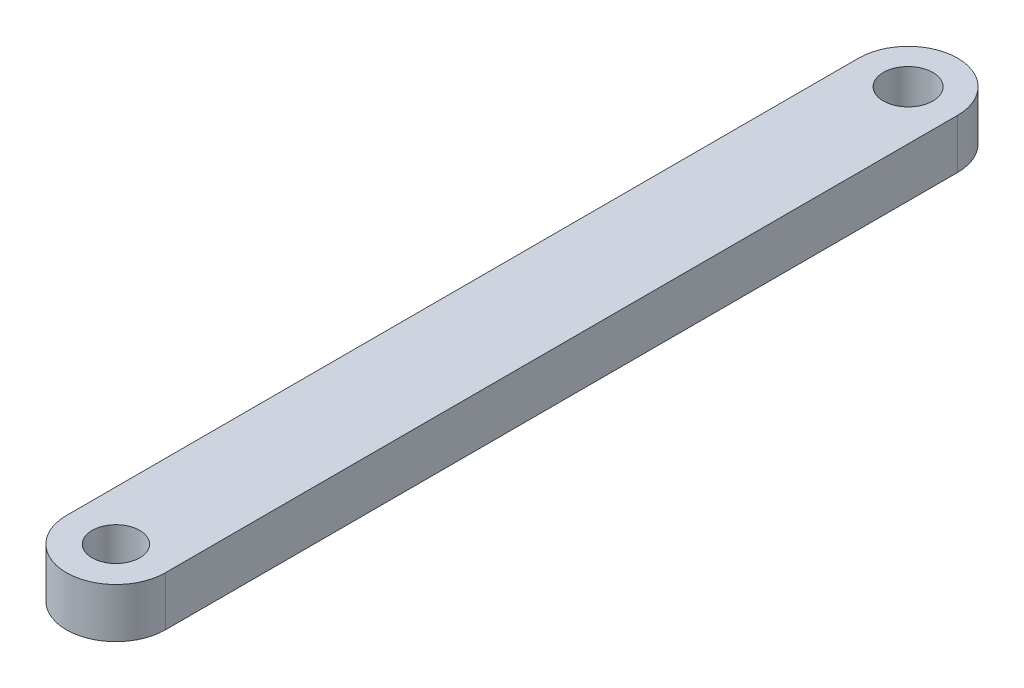
SolidWorks part; units mm, degrees
ref_plane "Front Plane" through (0, 0, 0) normal (0, 0, 1) x (1, 0, 0)
ref_plane "Top Plane" through (0, 0, 0) normal (0, 1, 0) x (1, 0, 0)
ref_plane "Right Plane" through (0, 0, 0) normal (1, 0, 0) x (0, 0, -1)
sketch "Sketch1" plane through (0, 0, 0) normal (0, 1, 0) x (1, 0, 0)
  line L1 (5, 0) -> (-5, 0)
  line L2 (5, 0) -> (5, 80)
  line L3 (-5, 0) -> (-5, 80)
  line L4 (5, 80) -> (-5, 80)
  circle A1 centre (0, 0) radius 5
  circle A2 centre (0, 80) radius 5
  circle A3 centre (0, 0) radius 2.4046
  circle A4 centre (0, 80) radius 2.5
  dimension "D1" = 80
  dimension "D2" = 10
  dimension "D3" = 5
extrude "Boss-Extrude3" add sketch "Sketch1" along normal blind 5 contours A3 L1 A1 | A3 L1 A1 | A2 L3 A1 L2 | A4 L4 A2 | A4 L4 A2 region at (0, 0, 2.4535) region at (0, 0, -40) region at (0, 0, -2.4535) region at (0, 0, -75.1118) region at (3.75, 0, -80.1118)
ref_axis "Axis2" through (0, 5, -80) along (0, -1, 0)
ref_axis "Axis3" through (0, 5, 0) along (0, -1, 0)
equation "\"Shaft_Diameter\"= 5mm"
